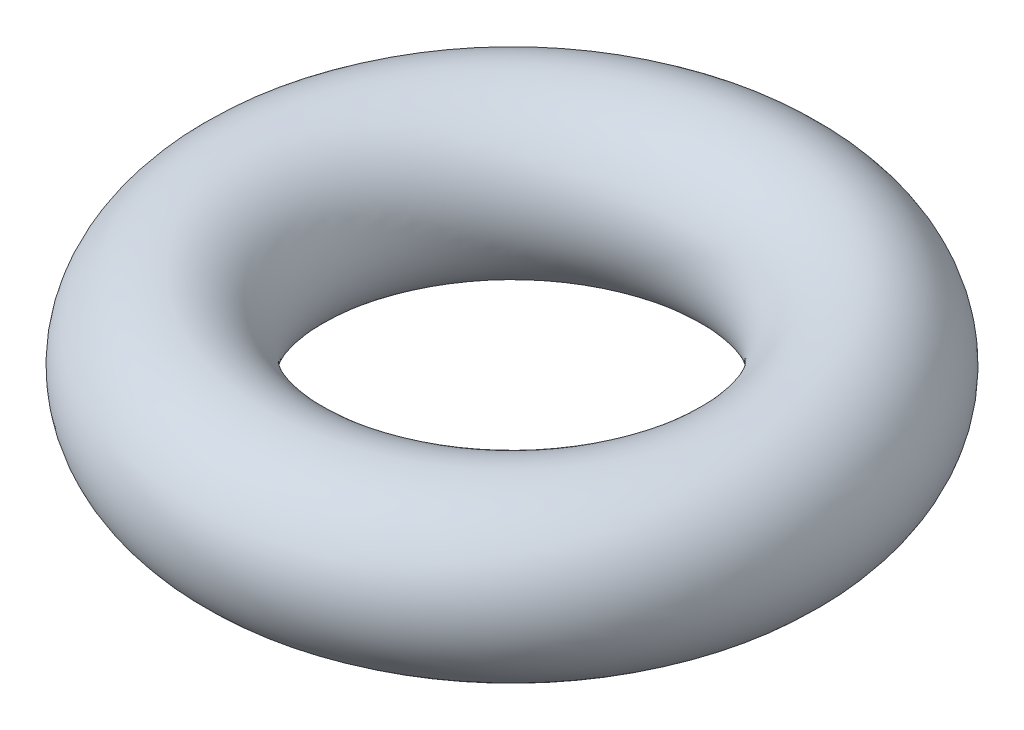
SolidWorks part; units mm, degrees
material "Silicon Rubber"
ref_plane "Front Plane" through (0, 0, 0) normal (0, 0, 1) x (1, 0, 0)
ref_plane "Top Plane" through (0, 0, 0) normal (0, 1, 0) x (1, 0, 0)
ref_plane "Right Plane" through (0, 0, 0) normal (1, 0, 0) x (0, 0, -1)
ref_axis "CentralAxis" through (0, 0.55, 0) along (0, -1, 0)
sketch "MainBodyS" plane through (0, 0, 0) normal (0, 0, 1) x (1, 0, 0)
  line L0 (0, 0) -> (1.5, 0) construction
  line L1 (0, 0) -> (0, -1) construction
  circle A0 centre (1.5, 0) radius 0.5
  point P3 (2, 0)
  point P6 (-2, 0)
  point P7 (-1, 0)
  point P8 (1, 0)
  dimension "Dia" = 1
  dimension "RefRevolve" = 1
  dimension "RevolveDia" = 3
  dimension "OD" = 4
  dimension "ID" = 2
revolve "MAIN BODY" add sketch "MainBodyS" angle 360 about L1
